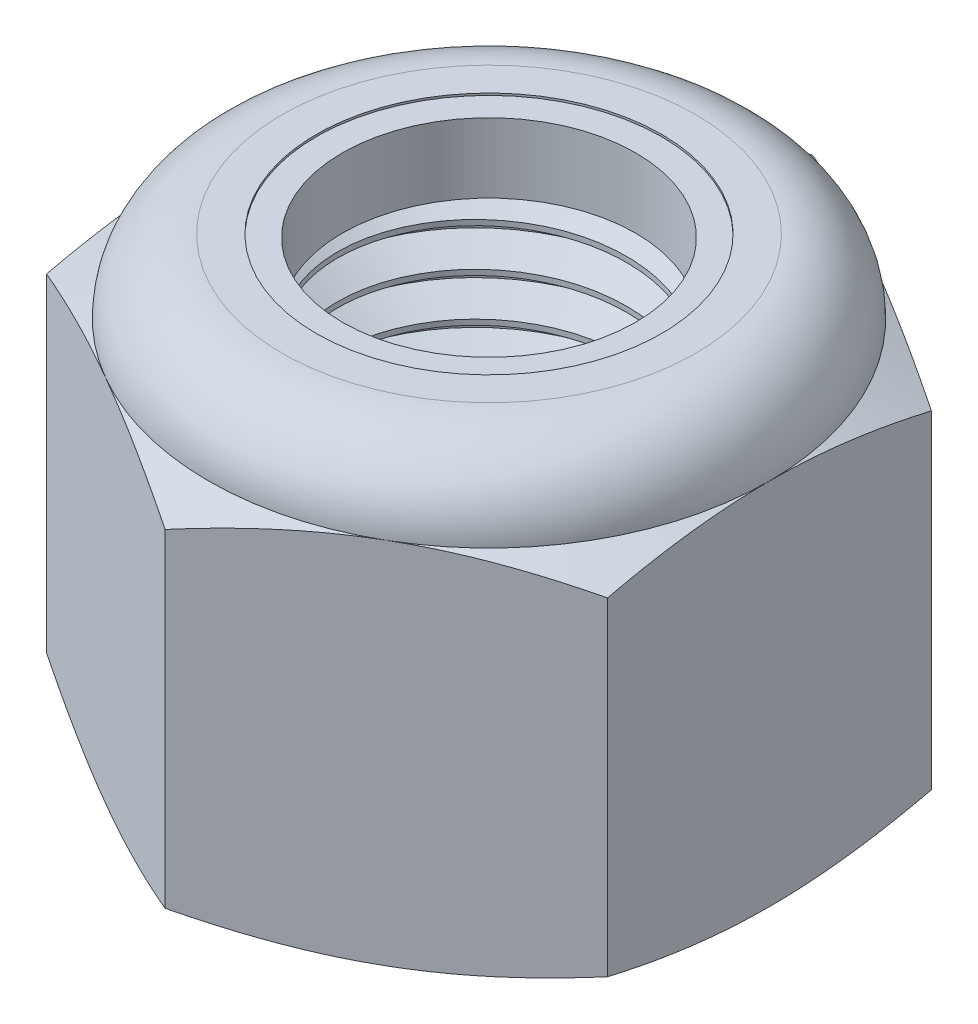
SolidWorks part; units mm, degrees
note: '?' marks a value the reader was unsure of.
ref_plane "Front" through (0, 0, 0) normal (0, 0, 1) x (1, 0, 0)
ref_plane "Top" through (0, 0, 0) normal (0, 1, 0) x (1, 0, 0)
ref_plane "Right" through (0, 0, 0) normal (1, 0, 0) x (0, 0, -1)
sketch "Sketch8" plane through (0, 0, 0) normal (1, 0, 0) x (0, 0, -1)
  line L0 (0, 0) -> (0, 32.5437) construction
  line L1 (20.6375, 0) -> (-20.6375, 0) construction
  line L2 (-12.7, 32.5437) -> (12.7, 32.5437) construction
  line L3 (12.7, 32.5437) -> (12.7, 29.3687) construction
sketch "Sketch1" plane through (0, 0, 0) normal (0, 1, 0) x (1, 0, 0)
  line L1 (0, 23.8301) -> (-20.6375, 11.9151)
  line L2 (-20.6375, 11.9151) -> (-20.6375, -11.9151)
  line L3 (-20.6375, -11.9151) -> (0, -23.8301)
  line L4 (0, -23.8301) -> (20.6375, -11.9151)
  line L5 (20.6375, -11.9151) -> (20.6375, 11.9151)
  line L6 (20.6375, 11.9151) -> (0, 23.8301)
  circle A0 centre (0, 0) radius 20.6375 construction
  circle A1 centre (0, 0) radius 12.7
extrude "Extrude1" add sketch "Sketch1" along normal up to vertex (32.5438 mm away) up to point (0, 32.5437, 0)
sketch "Sketch5" plane through (0, 0, 0) normal (1, 0, 0) x (0, 0, -1)
  line L0 (0, 0) -> (20.6375, 0)
  line L1 (20.6375, 0) -> (23.8301, 1.4887)
  line L2 (23.8301, 1.4887) -> (23.8301, 25.631)
  line L3 (23.8301, 25.631) -> (20.6375, 27.1198)
  line L4 (15.2135, 32.5437) -> (15.2135, 33.8137)
  line L5 (15.2135, 33.8137) -> (25.1001, 33.8137)
  line L6 (25.1001, 33.8137) -> (25.1001, -1.27)
  line L7 (25.1001, -1.27) -> (0, -1.27)
  line L8 (0, -1.27) -> (0, 0)
  line L9 (20.6375, 27.1198) -> (20.6375, 0) construction
  line L12 (23.8301, 32.5437) -> (23.8301, 0) construction
  line L13 (23.8301, 16.2719) -> (25.1001, 16.2719) construction
  line L15 (0, 0) -> (0, 33.8137) construction
  line L18 (20.6375, 0) -> (-20.6375, 0) construction
  line L19 (11.9151, 32.5437) -> (23.8301, 32.5437) construction
  line L20 (0, 33.8137) -> (15.2135, 33.8137) construction
  line L21 (11.9151, 0) -> (23.8301, 0) construction
  arc A0 (20.6375, 27.1198) -> (15.2135, 32.5437) centre (15.2135, 27.1198) ccw
  dimension "D1" = 25
  dimension "D2" = 1.27
  dimension "D4" = 5.424
revolve "Cut-Revolve3" cut sketch "Sketch5" angle 360 about L15
sketch "Sketch4" plane through (0, 0, 0) normal (1, 0, 0) x (0, 0, -1)
  line L0 (0, 27.1198) -> (13.97, 27.1198)
  line L1 (13.97, 27.1198) -> (0, 20.6055)
  line L3 (0, 6.5143) -> (13.97, 0)
  line L4 (13.97, 0) -> (0, 0)
  line L5 (0, 0) -> (0, 27.1198) construction
  line L10 (0, 0) -> (0, 32.5437) construction
  line L11 (0, 6.5143) -> (0, 0)
  line L12 (0, 27.1198) -> (0, 20.6055)
  line L13 (17.8726, 27.1198) -> (0, 27.1198) construction
  dimension "D1" = 25
  dimension "D2" = 27.94
sketch "Sketch6" plane through (0, 0, 0) normal (1, 0, 0) x (0, 0, -1)
  line L0 (0, 27.1198) -> (20.4851, 27.1198)
  line L1 (15.2135, 32.3914) -> (7.6068, 32.3914)
  line L2 (0, 33.8137) -> (0, 27.1198)
  line L3 (7.6068, 33.8137) -> (0, 33.8137)
  line L4 (0, 33.8137) -> (15.2135, 33.8137) construction
  line L5 (0, 0) -> (0, 33.8137) construction
  line L6 (0, 33.8137) -> (0, 0) construction
  line L7 (7.6068, 32.3914) -> (7.6068, 33.8137)
  line L8 (15.2135, 32.5437) -> (15.2135, 32.3914) construction
  line L9 (7.6068, 32.3914) -> (0, 32.3914) construction
  line L10 (0, 32.3914) -> (0, 20.6055) construction
  arc A0 (20.4851, 27.1198) -> (15.2135, 32.3914) centre (15.2135, 27.1198) ccw
  arc A1 (20.6375, 27.1198) -> (15.2135, 32.5437) centre (15.2135, 27.1198) ccw construction
  dimension "D1" = 0.1524
revolve "Cut-Revolve4" cut sketch "Sketch6" angle 360 about L6
revolve "Cut-Revolve2" cut sketch "Sketch4" angle 360 about L5
sketch "Sketch7" plane through (0, 0, 0) normal (1, 0, 0) x (0, 0, -1)
  line L0 (10.795, 27.196) -> (20.4083, 27.196)
  line L1 (15.2135, 32.3152) -> (10.795, 32.3152)
  line L2 (10.795, 32.3152) -> (10.795, 27.196)
  line L3 (10.795, 27.196) -> (0, 27.196) construction
  line L4 (0, 27.196) -> (0, 32.3152) construction
  line L5 (0, 32.3152) -> (10.795, 32.3152) construction
  line L6 (10.795, 27.196) -> (10.795, 27.1198) construction
  line L7 (0, 27.1198) -> (20.4851, 27.1198) construction
  line L8 (15.2135, 32.3152) -> (15.2135, 32.3914) construction
  arc A0 (20.4083, 27.196) -> (15.2135, 32.3152) centre (15.2135, 27.1198) ccw
  arc A2 (20.4851, 27.1198) -> (15.2135, 32.3914) centre (15.2135, 27.1198) ccw construction
  dimension "D1" = 0.0762
  dimension "D2" = 21.59
revolve "Revolve2" add sketch "Sketch7" angle 360 about L4
sketch "Sketch2" plane through (0, 0, 0) normal (1, 0, 0) x (0, 0, -1)
  line L0 (-12.7, 0) -> (-12.7, 27.1198) construction
  line L1 (0, 0) -> (12.7, 0)
  line L2 (0, 0) -> (0, 27.1198)
  line L3 (0, 27.1198) -> (12.7, 27.1198)
  line L4 (12.7, 0) -> (12.7, 27.1198)
  line L6 (17.8726, 27.1198) -> (20.6375, 27.1198) construction
  line L7 (0, -12.7) -> (0, 0) construction
revolve "Revolve1" add sketch "Sketch2" angle 360 about L7
sketch "Sketch9" plane through (0, 0, 0) normal (1, 0, 0) x (0, 0, -1)
  line L0 (13.0437, 30.0964) -> (13.0437, 26.9214) construction
  line L1 (13.0437, 26.9214) -> (10.2941, 28.5089) construction
  line L2 (10.2941, 28.5089) -> (13.0437, 30.0964) construction
  line L3 (10.6378, 28.7073) -> (10.6378, 28.3104) construction
  line L4 (12.7, 29.8979) -> (12.7, 27.1198) construction
  line L5 (10.2941, 28.5089) -> (10.6378, 28.5089) construction
  line L6 (12.7, 28.5089) -> (13.0437, 28.5089) construction
  line L7 (12.8719, 28.5089) -> (12.8719, 29.9971) construction
  line L8 (13.0437, 26.9214) -> (12.8719, 29.9971)
  line L9 (12.8719, 29.9971) -> (10.6378, 28.7073)
  line L10 (10.6378, 28.7073) -> (10.6378, 28.3104)
  line L11 (10.6378, 28.3104) -> (13.0437, 26.9214)
  dimension "D1" = 3.175
  dimension "D2" = 0.3969
sketch "Sketch10" plane through (0, 27.1198, 0) normal (0, 1, 0) x (1, 0, 0)
  circle A1 centre (0, 0) radius 12.7
  circle A2 centre (0, 0) radius 12.7
  dimension "D1" = 0
curve "Helix/Spiral1" pitch 3.175 height 35.7188 turns 11.25
sweep "Cut-Sweep1" cut profiles "Sketch9" path "Helix/Spiral1" align with end faces yes
sketch "Sketch11" plane through (0, 0, 0) normal (1, 0, 0) x (0, 0, -1)
  line L0 (0, 0) -> (0, 32.5437) construction
  line L1 (20.6375, 0) -> (-20.6375, 0) construction
  line L4 (0, 32.5437) -> (0, 0) construction
  line L5 (0, 16.2719) -> (12.7, 16.2719) construction
  line L6 (0, 0) -> (13.97, 0)
  line L7 (0, 6.5143) -> (0, 0)
  line L8 (13.97, 0) -> (0, 6.5143)
  dimension "D1" = 27.94
  dimension "D2" = 25
revolve "Revolve3" add sketch "Sketch11" angle 360 about L4
sketch "Sketch12" plane through (0, 0, 0) normal (1, 0, 0) x (0, 0, -1)
  line L0 (13.97, 27.1198) -> (0, 27.1198)
  line L1 (0, 27.1198) -> (0, 0)
  line L2 (0, 0) -> (13.97, 0)
  line L3 (20.6375, 0) -> (-20.6375, 0) construction
  line L4 (13.97, 0) -> (13.97, 27.1198)
  line L5 (-13.97, 0) -> (13.97, 0) construction
revolve "Revolve4" add sketch "Sketch12" angle 360 about L0
combine bodies "Combine1" operation type subtract main body 136 bodies to subtract 133
ref_plane "Contact Plane 1" through (0, 0, 0) normal (0, -1, 0) x (1, 0, 0)
ref_axis "Center Axis 1" through (0, -2.1015, 0) along (0, 1, 0)?
equation "\"D4@Sketch5\"=\"Height@Sketch8\"/6"
equation "\"D1@Sketch9\"=\"Thread Pitch@Sketch8\""
equation "\"D2@Sketch9\"=\"Thread Pitch@Sketch8\"/8"
equation "\"D4@Helix/Spiral1\"=\"Thread Pitch@Sketch8\""
equation "\"D3@Helix/Spiral1\"=\"Thread Pitch@Sketch8\"+\"Height@Sketch8\""
equation "\"D2@Sketch4\"=\"Thread Dia@Sketch8\"*1.1"
equation "\"D1@Sketch11\"=\"Thread Dia@Sketch8\"*1.1"
equation "\"D2@Sketch7\"=\"Thread Dia@Sketch8\"*.85"
